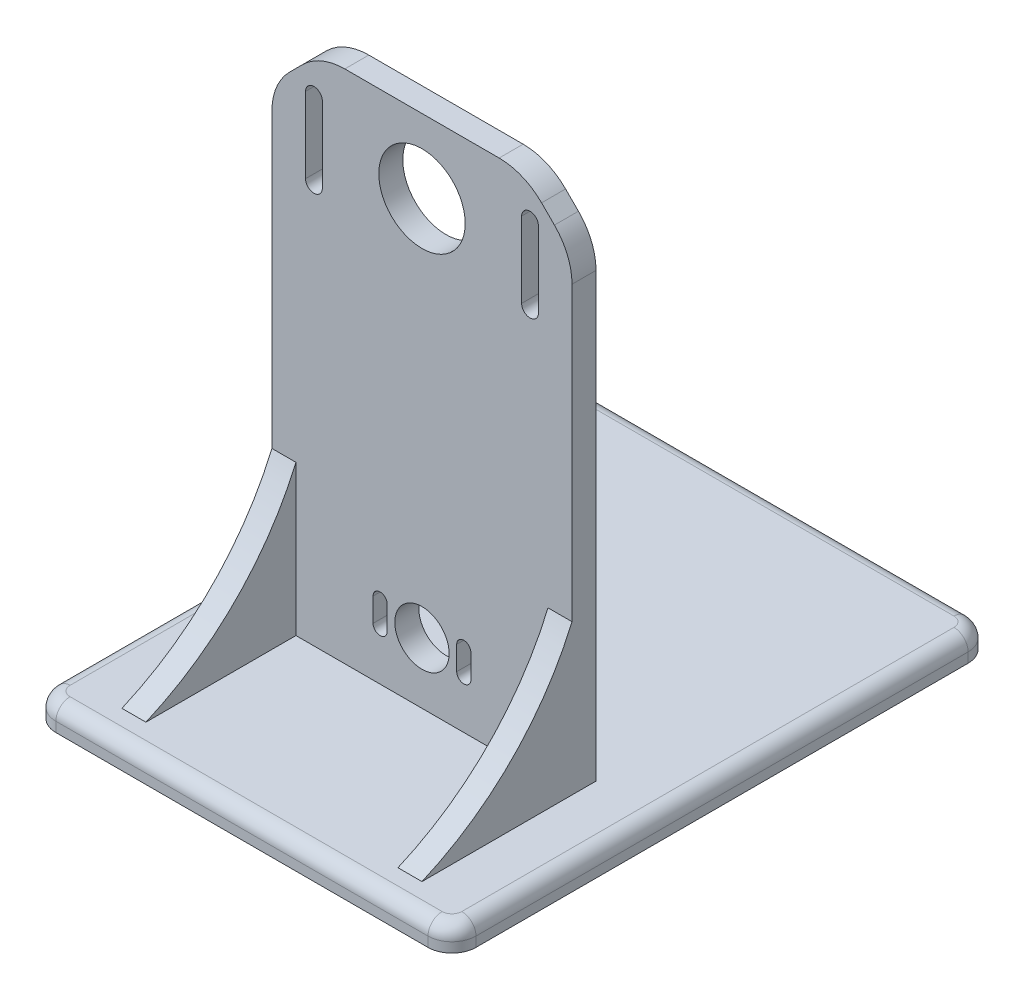
SolidWorks part; units mm, degrees
ref_plane "Front Plane" through (0, 0, 0) normal (0, 0, 1) x (1, 0, 0)
ref_plane "Top Plane" through (0, 0, 0) normal (0, 1, 0) x (1, 0, 0)
ref_plane "Right Plane" through (0, 0, 0) normal (1, 0, 0) x (0, 0, -1)
sketch "Sketch1" plane through (0, 0, 0) normal (0, 1, 0) x (1, 0, 0)
  line L1 (44.45, -57.15) -> (-44.45, -57.15)
  line L2 (44.45, -57.15) -> (44.45, 57.15)
  line L3 (44.45, 57.15) -> (-44.45, 57.15)
  line L4 (-44.45, -57.15) -> (-44.45, 57.15)
  line L5 (44.45, -57.15) -> (-44.45, 57.15) construction
  line L6 (44.45, 57.15) -> (-44.45, -57.15) construction
  point P0 (0, 0)
  dimension "D1" = 114.3
  dimension "D2" = 88.9
extrude "Base" add sketch "Sketch1" along normal blind 5.08
sketch "Sketch2" plane through (0, 5.08, 0) normal (0, 1, 0) x (1, 0, 0)
  line L0 (-44.45, 57.15) -> (-44.45, -57.15) construction
  line L1 (31.75, -13.97) -> (-31.75, -13.97)
  line L2 (31.75, -13.97) -> (31.75, -19.05)
  line L3 (31.75, -19.05) -> (-31.75, -19.05)
  line L4 (-31.75, -13.97) -> (-31.75, -19.05)
  line L5 (31.75, -13.97) -> (-31.75, -19.05) construction
  line L6 (31.75, -19.05) -> (-31.75, -13.97) construction
  line L7 (44.45, -57.15) -> (44.45, 57.15) construction
  line L8 (-44.45, -57.15) -> (44.45, -57.15) construction
  point P0 (0, -16.51)
  dimension "D1" = 5.08
  dimension "D2" = 63.5
  dimension "D3" = 12.7
  dimension "D4" = 12.7
  dimension "D5" = 38.1
extrude "Face Plate" add sketch "Sketch2" along normal blind 114.3
sketch "Sketch3" plane through (0, 0, 19.05) normal (0, 0, 1) x (1, 0, 0)
  line L0 (-31.75, 119.38) -> (-31.75, 5.08) construction
  line L1 (-31.75, 36.83) -> (-26.67, 36.83)
  line L2 (-31.75, 36.83) -> (-31.75, 5.08)
  line L3 (-31.75, 5.08) -> (-26.67, 5.08)
  line L4 (-26.67, 36.83) -> (-26.67, 5.08)
  line L5 (-31.75, 5.08) -> (31.75, 5.08) construction
  line L6 (31.75, 119.38) -> (31.75, 5.08) construction
  line L7 (31.75, 36.83) -> (26.67, 36.83)
  line L8 (31.75, 36.83) -> (31.75, 5.08)
  line L9 (31.75, 5.08) -> (26.67, 5.08)
  line L10 (26.67, 36.83) -> (26.67, 5.08)
  line L11 (-44.45, 5.08) -> (44.45, 5.08) construction
  dimension "D1" = 5.08
  dimension "D2" = 5.08
  dimension "D3" = 31.75
  dimension "D4" = 31.75
extrude "Back Face Supports" add sketch "Sketch3" along normal blind 31.75
sketch "Sketch4" plane through (31.75, 0, 0) normal (1, 0, 0) x (0, 0, -1)
  line L1 (-50.8, 5.08) -> (-50.8, 36.83)
  line L2 (-50.8, 36.83) -> (-19.05, 36.83)
  arc A0 (-50.8, 5.08) -> (-19.05, 36.83) centre (-74.6632, 60.6932) ccw
extrude "BF Extra Support Cut" cut sketch "Sketch4" against normal through all
sketch "Sketch5" plane through (0, 0, 19.05) normal (0, 0, 1) x (1, 0, 0)
  line L0 (31.75, 119.38) -> (31.75, 36.83) construction
  line L1 (-8.85, 15.48) -> (-8.85, 20.48) construction
  line L2 (22.86, 105.83) -> (22.86, 89.83) construction
  line L3 (-26.67, 5.08) -> (26.67, 5.08) construction
  line L4 (-10.35, 15.48) -> (-10.35, 20.48)
  line L5 (-7.35, 15.48) -> (-7.35, 20.48)
  line L6 (8.85, 20.48) -> (8.85, 15.48) construction
  line L7 (10.35, 20.48) -> (10.35, 15.48)
  line L8 (7.35, 20.48) -> (7.35, 15.48)
  line L9 (24.638, 105.83) -> (24.638, 89.83)
  line L10 (31.75, 119.38) -> (31.75, 36.83) construction
  line L11 (21.082, 105.83) -> (21.082, 89.83)
  line L13 (-22.86, 105.83) -> (-22.86, 89.83) construction
  line L14 (-21.082, 105.83) -> (-21.082, 89.83)
  line L15 (-44.45, 5.08) -> (44.45, 5.08) construction
  line L16 (-24.638, 105.83) -> (-24.638, 89.83)
  line L17 (-31.75, 119.38) -> (31.75, 119.38) construction
  circle A0 centre (0, 98.498) radius 9.144
  circle A2 centre (0, 17.98) radius 5.75
  arc A3 (-10.35, 15.48) -> (-7.35, 15.48) centre (-8.85, 15.48) ccw
  arc A4 (-7.35, 20.48) -> (-10.35, 20.48) centre (-8.85, 20.48) ccw
  arc A5 (10.35, 20.48) -> (7.35, 20.48) centre (8.85, 20.48) ccw
  arc A6 (7.35, 15.48) -> (10.35, 15.48) centre (8.85, 15.48) ccw
  arc A7 (24.638, 105.83) -> (21.082, 105.83) centre (22.86, 105.83) ccw
  arc A8 (21.082, 89.83) -> (24.638, 89.83) centre (22.86, 89.83) ccw
  arc A9 (-21.082, 105.83) -> (-24.638, 105.83) centre (-22.86, 105.83) ccw
  arc A10 (-24.638, 89.83) -> (-21.082, 89.83) centre (-22.86, 89.83) ccw
  point P10 (22.86, 97.83)
  point P15 (-8.85, 17.98)
  point P20 (8.85, 17.98)
  point P31 (-22.86, 97.83)
  dimension "D3" = 18.288
  dimension "D4" = 22.86
  dimension "D6" = 11.5
  dimension "D20" = 3.556
  dimension "D17" = 1.778
  dimension "D18" = 22.86
  dimension "D23" = 16
  dimension "D24" = 13.55
  dimension "D25" = 13.55
  dimension "D19" = 1.778
  dimension "D2" = 31.75
  dimension "D5" = 80.518
  dimension "D7" = 12.9
  dimension "D8" = 12.9
  dimension "D9" = 12.9
  dimension "D10" = 8.85
  dimension "D11" = 8.85
  dimension "D12" = 31.75
  dimension "D13" = 3
  dimension "D14" = 3
  dimension "D15" = 5
  dimension "D16" = 5
  dimension "D21" = 3.556
  dimension "D22" = 16
extrude "Face Holes" cut sketch "Sketch5" against normal through all
fillet "Base Corner Fillet" radius 5.08 4 edges at (-44.45, 2.54, -57.15) (44.45, 2.54, -57.15) (44.45, 2.54, 57.15) (-44.45, 2.54, 57.15)
sketch "Sketch9" plane through (0, 0, 19.05) normal (0, 0, 1) x (1, 0, 0)
  line L0 (-31.75, 114.0956) -> (31.75, 114.0956)
  line L1 (-31.75, 119.38) -> (-31.75, 36.83) construction
  line L2 (31.75, 119.38) -> (31.75, 36.83) construction
  line L3 (31.75, 114.0956) -> (31.75, 119.38)
  line L4 (31.75, 119.38) -> (-31.75, 119.38)
  line L5 (-31.75, 119.38) -> (-31.75, 114.0956)
extrude "Base Refine" cut sketch "Sketch9" against normal through all
sketch "Sketch10" plane through (0, 0, 19.05) normal (0, 0, 1) x (1, 0, 0)
  line L0 (-31.75, 103.9356) -> (-21.59, 114.0956)
  line L1 (-31.75, 114.0956) -> (-31.75, 36.83) construction
  line L2 (-31.75, 114.0956) -> (31.75, 114.0956) construction
  line L3 (-21.59, 114.0956) -> (-31.75, 114.0956)
  line L4 (-31.75, 114.0956) -> (-31.75, 103.9356)
  line L5 (21.59, 114.0956) -> (31.75, 103.9356)
  line L6 (31.75, 114.0956) -> (31.75, 36.83) construction
  line L7 (31.75, 103.9356) -> (31.75, 114.0956)
  line L8 (31.75, 114.0956) -> (21.59, 114.0956)
  dimension "D1" = 10.16
  dimension "D2" = 10.16
  dimension "D3" = 10.16
  dimension "D4" = 10.16
extrude "Face Refine Cut" cut sketch "Sketch10" against normal through all
fillet "Top Face Fillet" radius 12.7 4 edges at (-31.75, 103.9356, 16.51) (-21.59, 114.0956, 16.51) (31.75, 103.9356, 16.51) (21.59, 114.0956, 16.51)
sketch "Sketch13" plane through (0, 0, 13.97) normal (0, 0, -1) x (-1, 0, 0)
  line L0 (-31.75, 98.6751) -> (-31.75, 5.08) construction
  line L1 (-31.75, 17.78) -> (-26.67, 17.78)
  line L2 (-31.75, 17.78) -> (-31.75, 5.08)
  line L3 (-31.75, 5.08) -> (-26.67, 5.08)
  line L4 (-26.67, 17.78) -> (-26.67, 5.08)
  line L5 (-31.75, 5.08) -> (31.75, 5.08) construction
  line L7 (26.67, 17.78) -> (31.75, 17.78)
  line L8 (26.67, 17.78) -> (26.67, 5.08)
  line L9 (26.67, 5.08) -> (31.75, 5.08)
  line L10 (31.75, 17.78) -> (31.75, 5.08)
  dimension "D1" = 12.7
  dimension "D2" = 12.7
  dimension "D3" = 5.08
  dimension "D4" = 5.08
sketch "Sketch16" plane through (0, 0, 13.97) normal (0, 0, -1) x (-1, 0, 0)
  text T0 "hApkit\r\n" font "Century Schoolbook" height in points 24
extrude "Name" cut sketch "Sketch16" against normal blind 0.508
sketch "Sketch17" plane through (0, 0, 0) normal (0, -1, 0) x (1, 0, 0)
  line L0 (-41.91, 54.61) -> (0, 1.27)
  line L1 (0, 1.27) -> (41.91, 54.61)
  line L2 (41.91, 54.61) -> (-41.91, 54.61)
  line L3 (44.45, 52.07) -> (44.45, -52.07) construction
  line L4 (0, -1.27) -> (-41.91, -54.61)
  line L5 (-41.91, -54.61) -> (41.91, -54.61)
  line L6 (41.91, -54.61) -> (0, -1.27)
  line L7 (39.37, -57.15) -> (-39.37, -57.15) construction
  line L8 (-39.37, 57.15) -> (39.37, 57.15) construction
  line L9 (-44.45, -52.07) -> (-44.45, 52.07) construction
  line L10 (-41.91, -50.4988) -> (-41.91, 50.4747)
  line L11 (-41.91, 50.4747) -> (-2.2419, -0.012)
  line L12 (-2.2419, -0.012) -> (-41.91, -50.4988)
  line L13 (41.91, 50.4747) -> (41.91, -50.4988)
  line L14 (41.91, -50.4988) -> (2.2419, -0.012)
  line L15 (2.2419, -0.012) -> (41.91, 50.4747)
  dimension "D1" = 53.34
  dimension "D2" = 53.34
  dimension "D3" = 2.54
  dimension "D4" = 2.54
  dimension "D5" = 44.45
  dimension "D6" = 44.45
  dimension "D7" = 2.54
  dimension "D8" = 2.54
  dimension "D9" = 2.54
  dimension "D10" = 2.54
  dimension "D11" = 180
  dimension "D12" = 2.54
  dimension "D13" = 2.54
  dimension "D14" = 2.5549
  dimension "D15" = 180
  dimension "D16" = 180
  dimension "D17" = 2.54
extrude "Bottom Cut" cut sketch "Sketch17" against normal offset from surface (2.54 mm away) 2.54 up to face at (0, 5.08, 33.655)
fillet "Fillet1" radius 3 8 edges at (42.9621, 5.08, 55.6621) (-42.9621, 5.08, 55.6621) (-42.9621, 5.08, -55.6621) (42.9621, 5.08, -55.6621) (0, 5.08, 57.15) (-44.45, 5.08, 0) (0, 5.08, -57.15) (44.45, 5.08, 0)
sketch "Sketch19" plane through (0, 0, 13.97) normal (0, 0, -1) x (-1, 0, 0)
  text T0 "U" font "Century Gothic" height 5
extrude "Cut-Extrude1" cut sketch "Sketch19" against normal blind 0.4
